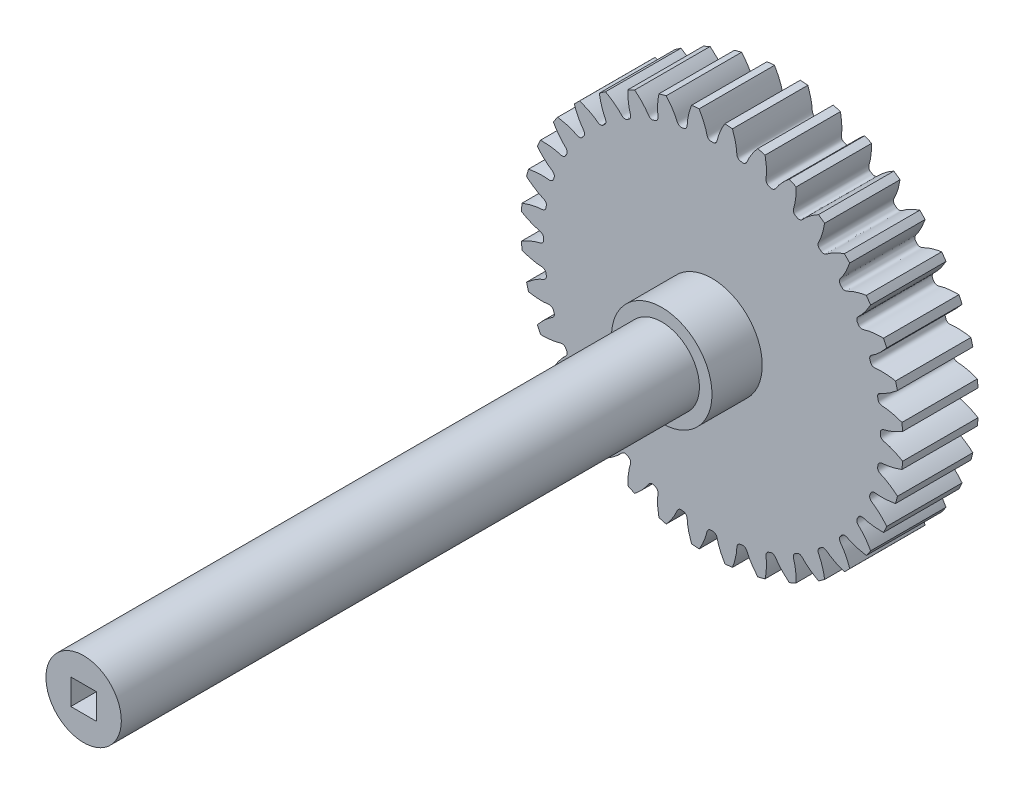
SolidWorks part; units mm, degrees
ref_plane "Front Plane" through (0, 0, 0) normal (0, 0, 1) x (1, 0, 0)
ref_plane "Top Plane" through (0, 0, 0) normal (0, 1, 0) x (1, 0, 0)
ref_plane "Right Plane" through (0, 0, 0) normal (1, 0, 0) x (0, 0, -1)
ref_axis "Axis1" through (0, 0, 55) along (0, 0, -1)
sketch "旋转草图大直齿轮" plane through (0, 0, 0) normal (1, 0, 0) x (0, 0, -1)
  line L0 (0, 0) -> (1, 0) construction
  line L1 (-7.5, 0) -> (-7.5, 38)
  line L2 (-7.5, 38) -> (7.5, 38)
  line L3 (7.5, 38) -> (7.5, 0)
  line L4 (7.5, 0) -> (-7.5, 0)
  dimension "Side1" = 7.5
  dimension "OutsideRadius" = 38
  dimension "Side2" = 7.5
revolve "大直齿轮" add sketch "旋转草图大直齿轮" angle 360 about L0
sketch "齿草图大直齿轮" plane through (0, 0, 0) normal (0, 0, 1) x (1, 0, 0)
  arc A0 (38.0098, 2.6196) -> (38.0098, -2.6196) centre (0, 0) cw
  spline S0 degree 3 poles (38.0098, -2.6196) (37.8138, -2.5003) (37.5223, -2.3306) (37.1351, -2.1211) (36.8604, -1.9796) (36.5956, -1.8501) (36.3411, -1.7319) (36.0971, -1.6246) (35.8641, -1.5278) (35.6423, -1.4409) (35.432, -1.3635) (35.2336, -1.295) (35.0473, -1.2349) (34.8734, -1.1827) (34.712, -1.138) (34.4981, -1.0822) (34.3156, -1.0475) (34.168, -1.0021) (34.1113, -0.9824) (34.0555, -0.9606) (34.0004, -0.9362) (33.9457, -0.9088) (33.891, -0.8777) (33.8362, -0.8418) (33.781, -0.7999) (33.7254, -0.7504) (33.6703, -0.6912) (33.617, -0.6201) (33.5685, -0.5354) (33.5291, -0.4365) (33.5051, -0.3307) (33.4954, -0.1836) (33.5031, 0) (33.4954, 0.1836) (33.5051, 0.3307) (33.5291, 0.4365) (33.5685, 0.5354) (33.617, 0.6201) (33.6703, 0.6912) (33.7254, 0.7504) (33.781, 0.7999) (33.8362, 0.8418) (33.891, 0.8777) (33.9457, 0.9088) (34.0004, 0.9362) (34.0555, 0.9606) (34.1113, 0.9824) (34.168, 1.0021) (34.3156, 1.0475) (34.4981, 1.0822) (34.712, 1.138) (34.8734, 1.1827) (35.0473, 1.2349) (35.2336, 1.295) (35.432, 1.3635) (35.6423, 1.4409) (35.8641, 1.5278) (36.0971, 1.6246) (36.3411, 1.7319) (36.5956, 1.8501) (36.8604, 1.9796) (37.1351, 2.1211) (37.5223, 2.3306) (37.8138, 2.5003) (38.0098, 2.6196) knots 0 0 0 0 0.062457 0.091761 0.119781 0.146518 0.171972 0.196143 0.21903 0.240634 0.260955 0.279993 0.297747 0.314218 0.329406 0.34331 0.374369 0.379859 0.385295 0.390713 0.396158 0.401682 0.407356 0.413263 0.419504 0.4262 0.433484 0.44149 0.450315 0.459977 0.470356 0.47968 0.5 0.52032 0.529644 0.540023 0.549685 0.55851 0.566516 0.5738 0.580496 0.586737 0.592644 0.598318 0.603842 0.609287 0.614705 0.620141 0.625631 0.65669 0.670594 0.685782 0.702253 0.720007 0.739045 0.759366 0.78097 0.803857 0.828028 0.853482 0.880219 0.908239 0.937543 1 1 1 1
extrude "齿拉伸切除大直齿轮" cut sketch "齿草图大直齿轮" against normal blind 7.5 and the other way blind 7.5
pattern_circular "齿形大直齿轮" count 36 every 10 about axis through (0, 0, 55) along (0, 0, -1) of "齿拉伸切除大直齿轮"
sketch "辅助草图大直齿轮" plane through (0, 0, 0) normal (0, 0, 1) x (1, 0, 0)
  circle A0 centre (0, 0) radius 36 construction
  circle A1 centre (0, 0) radius 33.8289 construction
  circle A2 centre (0, 0) radius 34.3848 construction
  circle A3 centre (0, 0) radius 38 construction
  circle A4 centre (0, 0) radius 33.5 construction
  dimension "PitchDiameter" = 72
  dimension "BaseDiameter" = 67.6579
  dimension "FormDiameter" = 68.7695
  dimension "MajorDiameter" = 76
  dimension "MinorDiameter" = 67
sketch "Sketch5" plane through (0, 0, 7.5) normal (0, 0, 1) x (1, 0, 0)
  circle A0 centre (0, 0) radius 10
  dimension "D1" = 20
extrude "Extrude2" add sketch "Sketch5" along normal blind 10
sketch "Sketch6" plane through (0, 0, 17.5) normal (0, 0, 1) x (1, 0, 0)
  circle A0 centre (0, 0) radius 7.5
  dimension "D1" = 15
extrude "Extrude3" add sketch "Sketch6" along normal blind 115
sketch "Sketch7" plane through (0, 0, 132.5) normal (0, 0, 1) x (1, 0, 0)
  line L1 (-2.55, 2.55) -> (2.55, 2.55)
  line L2 (-2.55, 2.55) -> (-2.55, -2.55)
  line L3 (-2.55, -2.55) -> (2.55, -2.55)
  line L4 (2.55, 2.55) -> (2.55, -2.55)
  line L5 (-2.55, 2.55) -> (2.55, -2.55) construction
  line L6 (-2.55, -2.55) -> (2.55, 2.55) construction
  point P0 (0, 0)
  dimension "D1" = 5.1
  dimension "D2" = 5.1
extrude "Extrude5" cut sketch "Sketch7" against normal blind 8
sketch "Sketch8" plane through (0, 0, 132.5) normal (0, 0, 1) x (1, 0, 0)
  line L0 (0, 0) -> (-7.5, 0)
  circle A0 centre (0, 0) radius 7.5 construction
